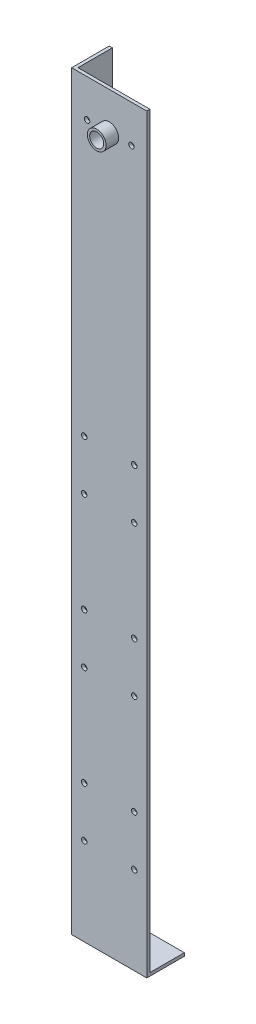
SolidWorks part; units mm, degrees
material "Galvanized Steel"
ref_plane "Front Plane" through (0, 0, 0) normal (0, 0, 1) x (1, 0, 0)
ref_plane "Top Plane" through (0, 0, 0) normal (0, 1, 0) x (1, 0, 0)
ref_plane "Right Plane" through (0, 0, 0) normal (1, 0, 0) x (0, 0, -1)
sketch "Sketch1" plane through (0, 0, 0) normal (0, 1, 0) x (1, 0, 0)
  line L1 (-76.2, -38.1) -> (76.2, -38.1)
  line L2 (-76.2, -38.1) -> (-76.2, 38.1)
  line L3 (-76.2, 38.1) -> (76.2, 38.1)
  line L4 (76.2, -38.1) -> (76.2, 38.1)
  line L5 (-76.2, -38.1) -> (76.2, 38.1) construction
  line L6 (-76.2, 38.1) -> (76.2, -38.1) construction
  point P0 (0, 0)
  dimension "D1" = 152.4
  dimension "D2" = 76.2
extrude "Boss-Extrude1" add sketch "Sketch1" along normal blind 1524
sketch "Sketch2" plane through (0, 0, 38.1) normal (0, 0, 1) x (1, 0, 0)
  line L1 (76.2, 1524) -> (76.2, 0) construction
  circle A0 centre (0, 1447.8) radius 6.35
  dimension "D1" = 12.7
  dimension "D2" = 1447.8
  dimension "D3" = 76.2
extrude "Cut-Extrude1" cut sketch "Sketch2" against normal up to next
sketch "Sketch4" plane through (0, 0, 38.1) normal (0, 0, 1) x (1, 0, 0)
  circle A0 centre (0, 1447.8) radius 14.2875
  circle A1 centre (0, 1447.8) radius 19.05
  dimension "D1" = 38.1
  dimension "D2" = 28.575
extrude "Boss-Extrude2" add sketch "Sketch4" along normal blind 25.4
sketch "Sketch5" plane through (0, 1524, 0) normal (0, 1, 0) x (1, 0, 0)
  line L4 (-69.85, 31.75) -> (-69.85, 38.1)
  line L5 (76.2, 38.1) -> (-76.2, 38.1) construction
  line L6 (-69.85, 38.1) -> (76.2, 38.1)
  line L7 (76.2, 38.1) -> (76.2, -31.75)
  line L9 (69.85, -31.75) -> (69.85, 31.75)
  line L20 (69.85, 31.75) -> (-69.85, 31.75)
  line L32 (-69.85, 31.75) -> (-69.85, -31.75)
  line L33 (-69.85, -31.75) -> (69.85, -31.75)
  line L36 (-69.85, 31.75) -> (-69.85, -31.75)
  line L37 (-69.85, -31.75) -> (69.85, -31.75)
  line L38 (76.2, -38.1) -> (76.2, 38.1) construction
  line L39 (76.2, -31.75) -> (69.85, -31.75)
  dimension "D1" = 6.35
extrude "Cut-Extrude3" cut sketch "Sketch5" against normal up to next
sketch "Sketch7" plane through (0, 0, 0) normal (0, -1, 0) x (1, 0, 0)
  line L1 (-76.2, -38.1) -> (76.2, -38.1)
  line L2 (-76.2, -38.1) -> (-76.2, 38.1)
  line L3 (-76.2, 38.1) -> (76.2, 38.1)
  line L4 (76.2, -38.1) -> (76.2, 38.1)
extrude "Boss-Extrude3" add sketch "Sketch7" against normal blind 6.35
sketch "Sketch8" plane through (0, 0, 31.75) normal (0, 0, -1) x (-1, 0, 0)
  line L0 (-76.2, 6.35) -> (-76.2, 1524) construction
  circle A0 centre (45.0453, 1447.8) radius 5.5562
  circle A1 centre (-45.0453, 1447.8) radius 5.5562
  dimension "D1" = 11.1125
  dimension "D2" = 90.0906
  dimension "D3" = 31.1547
extrude "Cut-Extrude4" cut sketch "Sketch8" against normal up to next
sketch "Sketch9" plane through (0, 0, 38.1) normal (0, 0, 1) x (1, 0, 0)
  line L1 (-76.2, 1524) -> (-76.2, 0) construction
  line L2 (76.2, 1524) -> (76.2, 0) construction
  line L3 (-76.2, 0) -> (76.2, 0) construction
  circle A0 centre (-50.8, 279.4) radius 5.5563
  circle A1 centre (50.8, 279.4) radius 5.5563
  circle A2 centre (50.8, 177.8) radius 5.5562
  circle A3 centre (-50.8, 177.8) radius 5.5562
  circle A4 centre (-50.8, 482.6) radius 5.5563
  circle A5 centre (50.8, 482.6) radius 5.5563
  circle A6 centre (-50.8, 584.2) radius 5.5563
  circle A7 centre (50.8, 584.2) radius 5.5563
  circle A8 centre (-50.8, 787.4) radius 5.5563
  circle A9 centre (50.8, 787.4) radius 5.5563
  circle A10 centre (50.8, 889) radius 5.5563
  circle A11 centre (-50.8, 889) radius 5.5563
  dimension "D1" = 11.1125
  dimension "D5" = 11.1125
  dimension "D8" = 101.6
  dimension "D9" = 11.1125
  dimension "D10" = 203.2
  dimension "D12" = 101.6
  dimension "D13" = 101.6
  dimension "D14" = 101.6
  dimension "D2" = 25.4
  dimension "D3" = 25.4
  dimension "D4" = 101.6
  dimension "D6" = 177.8
  dimension "D7" = 203.2
  dimension "D11" = 101.6
extrude "Cut-Extrude5" cut sketch "Sketch9" against normal up to next
